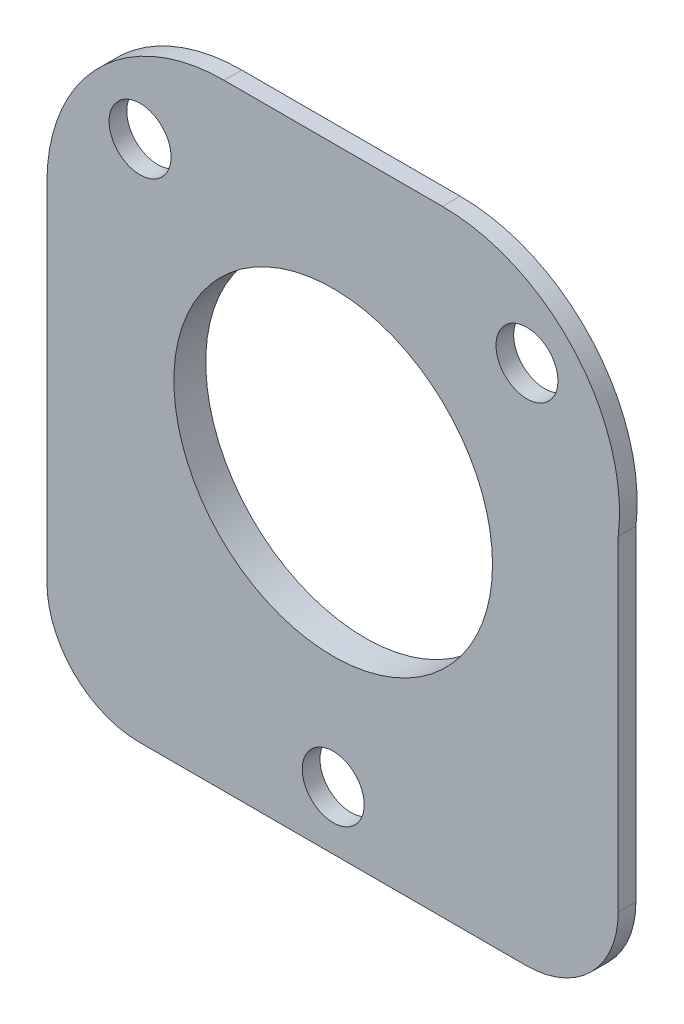
SolidWorks part; units mm, degrees
material "PET"
ref_plane "Piano frontale" through (0, 0, 0) normal (0, 0, 1) x (1, 0, 0)
ref_plane "Piano superiore" through (0, 0, 0) normal (0, 1, 0) x (1, 0, 0)
ref_plane "Piano destro" through (0, 0, 0) normal (1, 0, 0) x (0, 0, -1)
sketch "Schizzo1" plane through (0, 0, 0) normal (0, 0, 1) x (1, 0, 0)
  line L0 (-6.1713, 16.1) -> (6.1713, 16.1) construction
  line L1 (-6.1713, 16.1) -> (6.1713, 16.1)
  line L2 (-16.1713, 6.1) -> (-16.1713, -13.4632)
  line L3 (-10.9575, -18.677) -> (10.8862, -18.677)
  line L4 (16.1, -13.4632) -> (16.1, 4.9079)
  line L5 (-10.9107, 10.852) -> (-13.2424, 13.1711) construction
  line L6 (0, -15.3886) -> (-0.0357, -18.677) construction
  circle A0 centre (0, -15.3886) radius 1.25 construction
  circle A1 centre (0, 0) radius 12.1 construction
  circle A2 centre (-10.9107, 10.852) radius 1.25 construction
  circle A3 centre (10.9445, 10.818) radius 1.25 construction
  arc A4 (16.1, 4.9079) -> (6.1713, 16.1) centre (6.1713, 6.1) ccw construction
  arc A5 (-6.1713, 16.1) -> (-16.1713, 6.1) centre (-6.1713, 6.1) ccw construction
  circle A6 centre (0, -15.3886) radius 1.25
  circle A7 centre (0, 0) radius 12.1
  circle A8 centre (-10.9107, 10.852) radius 1.25
  circle A9 centre (10.9445, 10.818) radius 1.25
  arc A10 (16.1, 4.9079) -> (6.1713, 16.1) centre (6.1713, 6.1) ccw
  arc A11 (-6.1713, 16.1) -> (-16.1713, 6.1) centre (-6.1713, 6.1) ccw
  arc A12 (-16.1713, -13.4632) -> (-10.9575, -18.677) centre (-10.9575, -13.4632) ccw
  arc A13 (10.8862, -18.677) -> (16.1, -13.4632) centre (10.8862, -13.4632) ccw
  circle A14 centre (-10.9107, 10.852) radius 1.75
  circle A15 centre (10.9445, 10.818) radius 1.75
  circle A16 centre (0, -15.3886) radius 1.75
  dimension "D1" = 3.5
extrude "Estrusione-Estrusione1" add sketch "Schizzo1" along normal blind 1 contours L3 A13 L4 A10 L1 A11 L2 A12 A16 A15 A14 A7 region at (0, 15.6251, 0)
sketch "Schizzo2" plane through (0, 0, 1) normal (0, 0, 1) x (1, 0, 0)
  circle A0 centre (0, 0) radius 9 construction
  circle A1 centre (0, 0) radius 9
  circle A2 centre (0, 0) radius 12.1 construction
  circle A3 centre (0, 0) radius 12.1
extrude "Estrusione-Estrusione2" add sketch "Schizzo2" against normal blind 1.8
